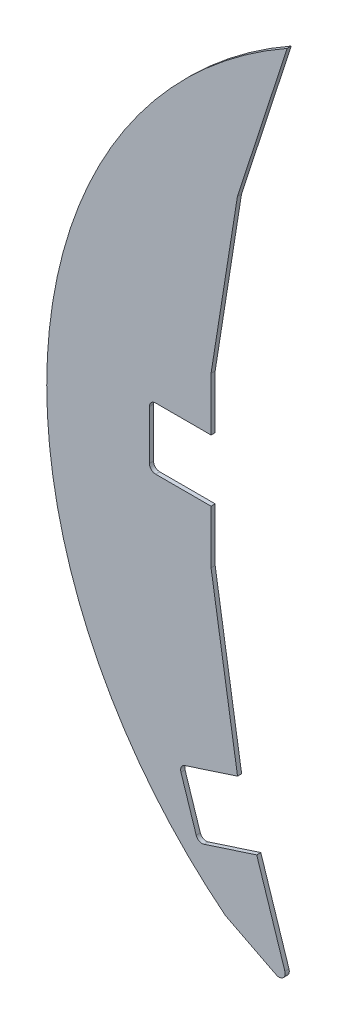
SolidWorks part; units mm, degrees
material "AISI 1020"
ref_plane "Спереди" through (0, 0, 0) normal (0, 0, 1) x (1, 0, 0)
ref_plane "Сверху" through (0, 0, 0) normal (0, 1, 0) x (1, 0, 0)
ref_plane "Справа" through (0, 0, 0) normal (1, 0, 0) x (0, 0, -1)
sketch "Эскиз1" plane through (0, 0, 0) normal (0, 0, 1) x (1, 0, 0)
  line L0 (-28.3889, 12) -> (-28.3889, -12) construction
  line L1 (-28.3889, 12) -> (-28.3889, -12)
  line L2 (-13.0429, -134.5024) -> (-5.6265, -157.3277) construction
  line L3 (-13.0429, -134.5024) -> (-5.6265, -157.3277)
  line L4 (33.3292, -196.7119) -> (8.5972, -184.1103) construction
  line L5 (33.3292, -196.7119) -> (8.5972, -184.1103)
  line L6 (37.5444, -193.1118) -> (23.8323, -150.9104)
  line L7 (14.5618, -122.3787) -> (37.5444, -193.1118) construction
  line L8 (23.8323, -150.9104) -> (-1.8462, -159.2538)
  line L9 (-1.8462, -159.2538) -> (20.9791, -151.8374) construction
  line L10 (-11.1167, -130.7221) -> (14.5025, -122.3979)
  line L11 (14.5025, -122.3979) -> (1.6111, -41.0047)
  line L12 (1.6111, -41.0047) -> (1.6111, -15)
  line L13 (1.6111, -15) -> (-25.3889, -15)
  line L14 (-25.3889, -15) -> (-1.3889, -15) construction
  line L15 (1.6111, 40.6112) -> (1.6111, -40.6112) construction
  line L16 (1.6726, -41.3934) -> (14.3786, -121.6158) construction
  line L17 (11.7086, -123.3057) -> (-11.1167, -130.7221) construction
  line L18 (-25.3889, 15) -> (1.6111, 15)
  line L19 (1.6111, 15) -> (1.6111, 41.0047)
  line L20 (1.6111, 41.0047) -> (14.4402, 122.0044)
  line L21 (14.4402, 122.0044) -> (38.6599, 196.5451)
  line L22 (14.3786, 121.6158) -> (1.6726, 41.3934) construction
  line L23 (38.6599, 196.5451) -> (14.5618, 122.3787) construction
  arc A0 (38.6599, 196.5451) -> (8.5972, -184.1103) centre (151.7704, -3.9028) ccw
  arc A1 (-28.3889, -12) -> (-25.3889, -15) centre (-25.3889, -12) ccw construction
  arc A2 (-25.3889, 15) -> (-28.3889, 12) centre (-25.3889, 12) ccw construction
  arc A3 (-28.3889, -12) -> (-25.3889, -15) centre (-25.3889, -12) ccw
  arc A4 (-25.3889, 15) -> (-28.3889, 12) centre (-25.3889, 12) ccw
  arc A5 (-5.6265, -157.3277) -> (-1.8462, -159.2538) centre (-2.7733, -156.4007) ccw construction
  arc A6 (-11.1167, -130.7221) -> (-13.0429, -134.5024) centre (-10.1897, -133.5753) ccw construction
  arc A7 (-5.6265, -157.3277) -> (-1.8462, -159.2538) centre (-2.7733, -156.4007) ccw
  arc A8 (-11.1167, -130.7221) -> (-13.0429, -134.5024) centre (-10.1897, -133.5753) ccw
  arc A9 (33.3292, -196.7119) -> (37.5444, -193.1118) centre (34.6912, -194.0389) ccw construction
  arc A10 (33.3292, -196.7119) -> (37.5444, -193.1118) centre (34.6912, -194.0389) ccw
  dimension "D1" = 50
base flange "Базовая кромка1" sketch "Эскиз1" thickness 2 reverse thickness direction no parameters "D1"=3
sketch "Сгиб-Линии1" [suppressed] plane through (0, 0, 0) normal (0, 1, 0) x (1, 0, 0)
sketch "Граничная рамка1" [suppressed] plane through (0, 0, 0) normal (0, 1, 0) x (1, 0, 0)
sheet metal parameters "Листовой металл3" thickness 2 parameters "D1"=3
flat pattern "Развертка3" [suppressed]
sketch "Сгиб-Линии2" plane through (0, 0, 0) normal (0, 1, 0) x (1, 0, 0)
sketch3d "Граничная рамка2" [suppressed]
  line L0 (-114.0867, -193.1436, 0) -> (-113.1105, 200.4478, 0) construction
  line L1 (-230.6384, -192.8545, 0) -> (-229.6622, 200.7369, 0) construction
  line L2 (-114.0867, -193.1436, 0) -> (-230.6384, -192.8545, 0) construction
  line L3 (-113.1105, 200.4478, 0) -> (-229.6622, 200.7369, 0) construction
